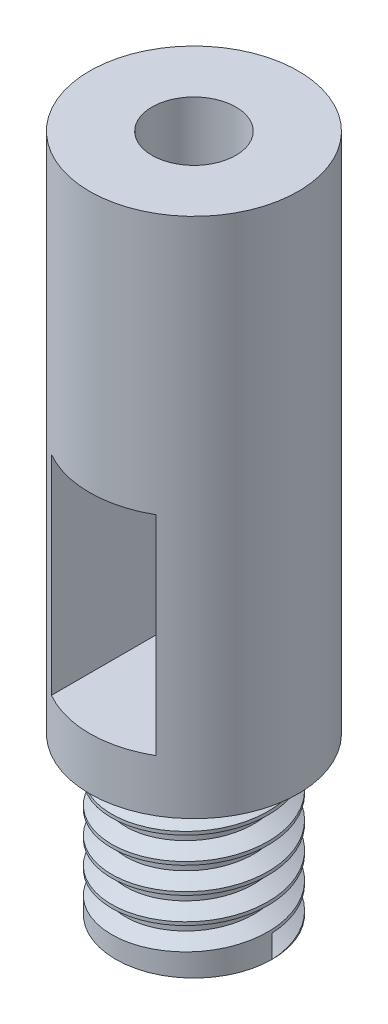
SolidWorks part; units mm, degrees
material "6061 Alloy"
ref_plane "Front Plane" through (0, 0, 0) normal (0, 0, 1) x (1, 0, 0)
ref_plane "Top Plane" through (0, 0, 0) normal (0, 1, 0) x (1, 0, 0)
ref_plane "Right Plane" through (0, 0, 0) normal (1, 0, 0) x (0, 0, -1)
sketch "Sketch1" plane through (0, 0, 0) normal (0, 1, 0) x (1, 0, 0)
  circle A0 centre (0, 0) radius 4.7625
  dimension "D1" = 9.525
extrude "Boss-Extrude1" add sketch "Sketch1" against normal blind 9.525
sketch "Sketch2" plane through (0, 0, 0) normal (0, 1, 0) x (1, 0, 0)
  circle A0 centre (0, 0) radius 6.35
  dimension "D1" = 12.7
extrude "Boss-Extrude2" add sketch "Sketch2" along normal blind 31.75
sketch "Sketch3" plane through (0, 0, 0) normal (0, 0, 1) x (1, 0, 0)
  line L0 (0, 0) -> (0, 3.175) construction
  line L1 (-3.175, 3.175) -> (3.175, 3.175)
  line L2 (-3.175, 3.175) -> (-3.175, 15.875)
  line L3 (-3.175, 15.875) -> (3.175, 15.875)
  line L4 (3.175, 3.175) -> (3.175, 15.875)
  dimension "D1" = 3.175
  dimension "D2" = 6.35
  dimension "D3" = 12.7
extrude "Cut-Extrude1" cut sketch "Sketch3" against normal through all both and the other way through all
hole_wizard "1/4-20 Tapped Hole1" positions "Sketch4" profile "Sketch5" tap size "1/4-20" standard "ANSI Inch" end condition up to next
sketch "Sketch4" plane through (0, 31.75, 0) normal (0, 1, 0) x (1, 0, 0)
  point P0 (0, 0)
sketch "Sketch5" plane through (0, 31.75, 0) normal (1, 0, 0) x (0, 0, 1)
  line L0 (0, 0) -> (0, 15.875)
  line L1 (0, 15.875) -> (2.5527, 15.875)
  line L2 (2.5527, 15.875) -> (2.5527, 0)
  line L5 (2.5527, 0) -> (0, 0)
  line L11 (0, -6.35) -> (0, 107.95) construction
  dimension "Thru Tap Drill Dia." = 5.1054
  dimension "Thru Tap Drill Depth" = 15.875
cosmetic thread "Hole Thread1" parameters "D2"=6.35
thread "Thread1" pitch 1.5875 method cut profile "Thread Profile1" start angle 0, offset 0, length 9.525, pitch 1.5875, diameter 9.525
ref_plane "Plane1" through (4.7625, -9.525, 0) normal (0, 0, 1) x (1, 0, 0)
sketch "Thread Profile1" plane through (4.7625, -9.525, 0) normal (0, 0, 1) x (1, 0, 0)
  line L0 (0, 0) -> (0, 1.5875) construction
  line L11 (0, 0) -> (0, 1.3891)
  line L12 (0, 1.3891) -> (-0.8593, 0.893)
  line L13 (-0.8593, 0.893) -> (-0.8593, 0.4961)
  line L15 (-0.8593, 0.4961) -> (0, 0)
  line L17 (-0.8593, 0.6945) -> (0, 0.6945) construction
  point P2 (0, 0)
  dimension "Pitch" = 1.5875
  dimension "Profile_Angle" = 60
  dimension "Profile_Land" = 0.3969
  dimension "Profile_Height" = 0.8593
